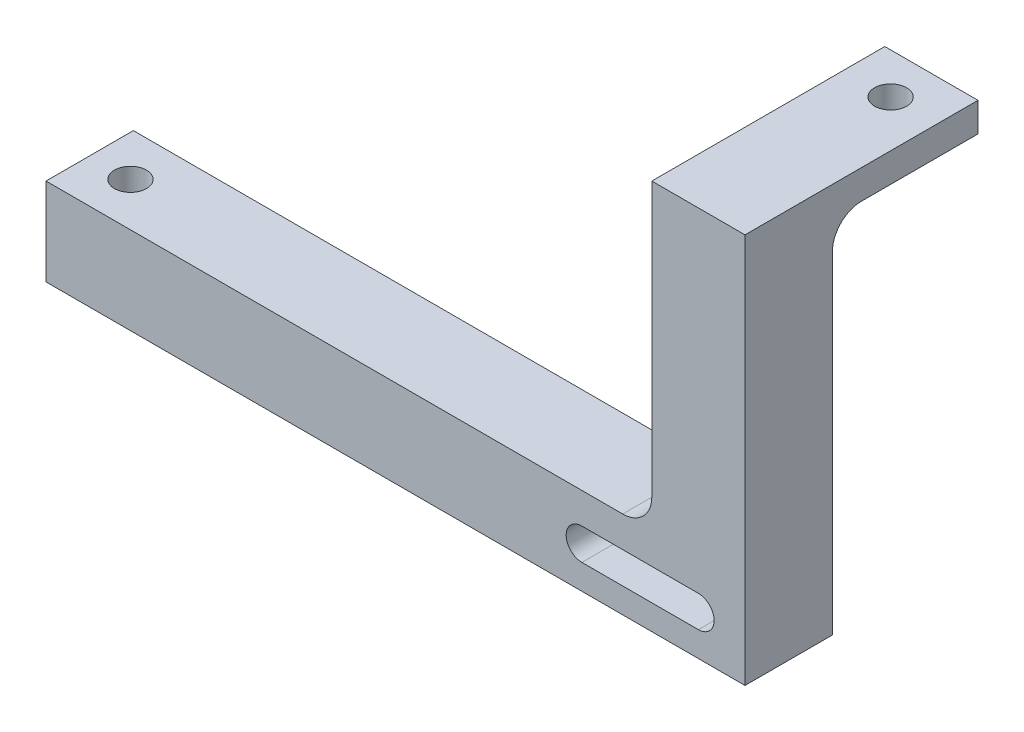
SolidWorks part; units mm, degrees
ref_plane "Front Plane" through (0, 0, 0) normal (0, 0, 1) x (1, 0, 0)
ref_plane "Top Plane" through (0, 0, 0) normal (0, 1, 0) x (1, 0, 0)
ref_plane "Right Plane" through (0, 0, 0) normal (1, 0, 0) x (0, 0, -1)
ref_axis "X" through (6, 0, 0) along (-1, 0, 0)
ref_axis "Y" through (0, 36.75, 0) along (0, -1, 0)
ref_axis "Z" through (0, 0, -32.25) along (0, 0, 1)
sketch "Sketch1" plane through (0, 0, 0) normal (0, 0, 1) x (1, 0, 0)
  line L0 (0, 0) -> (-120, 0)
  line L2 (-16, 62) -> (0, 62)
  line L3 (0, 62) -> (0, 0)
  line L4 (-120, 15) -> (-16, 15)
  line L6 (-120, 0) -> (-120, 15)
  line L7 (-16, 62) -> (-16, 15)
  point P7 (-1.1501, 0)
  point P8 (0, 0)
  dimension "D1" = 15
  dimension "D2" = 16
  dimension "D3" = 62
extrude "Boss-Extrude1" add sketch "Sketch1" along normal blind 15
sketch "Sketch2" plane through (0, 0, 15) normal (0, 0, 1) x (1, 0, 0)
  line L0 (0, 0) -> (0, 62) construction
  line L1 (-16, 62) -> (0, 62)
  line L2 (-16, 62) -> (-16, 67)
  line L3 (-16, 67) -> (0, 67)
  line L4 (0, 62) -> (0, 67)
  point P7 (-16, 30)
  point P9 (0, 30)
  dimension "D1" = 5
extrude "Boss-Extrude2" add sketch "Sketch2" against normal blind 40
sketch "Sketch3" plane through (0, 0, 15) normal (0, 0, 1) x (1, 0, 0)
  line L0 (-28, 7) -> (-8, 7) construction
  line L1 (-28, 9.7) -> (-8, 9.7)
  line L2 (-28, 4.3) -> (-8, 4.3)
  line L3 (-120, 0) -> (0, 0) construction
  line L5 (0, 0) -> (0, 67) construction
  arc A0 (-28, 9.7) -> (-28, 4.3) centre (-28, 7) ccw
  arc A1 (-8, 4.3) -> (-8, 9.7) centre (-8, 7) ccw
  point P2 (-18, 7)
  dimension "D1" = 7
  dimension "D2" = 5.4
  dimension "D3" = 8
  dimension "D4" = 20
extrude "Cut-Extrude1" cut sketch "Sketch3" against normal blind 45
hole_wizard "M5 Clearance Hole1" positions "Sketch4" profile "Sketch5" hole size "M5" standard "DIN" end condition up to next
sketch "Sketch4" plane through (0, 67, 0) normal (0, 1, 0) x (1, 0, 0)
  line L0 (-8, 25) -> (-8, 18) construction
  line L1 (0, 25) -> (-16, 25) construction
  line L4 (-120, -7.5) -> (-113, -7.5) construction
  line L6 (-120, -15) -> (-120, 0) construction
  point P0 (-8, 18)
  point P2 (-113, -7.5)
  point P16 (-58.9096, -8.0682)
  point P17 (-120, -7.5)
  point P20 (-113.5251, -4.8401)
  dimension "D1" = 7
  dimension "D2" = 7
sketch "Sketch5" plane through (-8, 67, -18) normal (1, 0, 0) x (0, 0, 1)
  line L0 (0, 0) -> (0, 5)
  line L1 (0, 5) -> (2.75, 5)
  line L2 (2.75, 5) -> (2.75, 0)
  line L5 (2.75, 0) -> (0, 0)
  line L11 (0, -6.35) -> (0, 107.95) construction
  dimension "Thru Hole Dia." = 5.5
  dimension "Thru Hole Depth" = 5
fillet "Fillet1" radius 5 2 edges at (-8, 62, 0) (-16, 15, 7.5)
